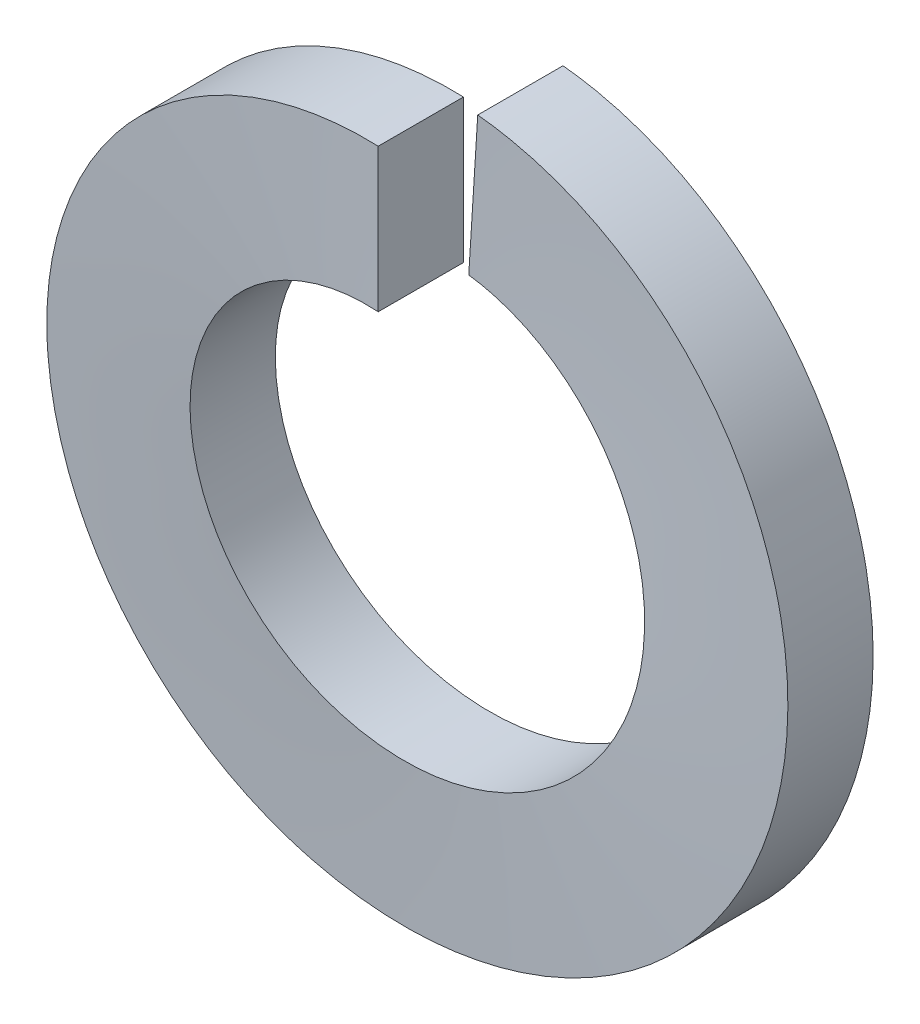
SolidWorks part; units mm, degrees
ref_plane "Front Plane" through (0, 0, 0) normal (0, 0, 1) x (1, 0, 0)
ref_plane "Top Plane" through (0, 0, 0) normal (0, 1, 0) x (1, 0, 0)
ref_plane "Right Plane" through (0, 0, 0) normal (1, 0, 0) x (0, 0, -1)
sketch "Sketch1" plane through (0, 0, 0) normal (0, 0, 1) x (1, 0, 0)
  line L0 (0, 9.05) -> (0, 5.35) construction
  line L2 (0, -2.1) -> (0, 2.1) construction
  circle A0 centre (0, 0) radius 9.05 construction
  circle A1 centre (0, 0) radius 5.35 construction
  point P6 (5.35, 0)
  point P7 (-9.05, 0)
  point P8 (-5.35, 0)
  point P9 (0, 0)
  point P10 (9.05, 0)
  point P14 (0, 0)
  point P15 (0, 2.1)
  point P16 (0, -2.1)
  dimension "Overall Height" = 4.2
  dimension "ID" = 10.7
  dimension "OD" = 18.1
sketch "Sketch2" plane through (0, 0, 0) normal (1, 0, 0) x (0, 0, -1)
  line L1 (0, 9.05) -> (-2.2, 9.05) construction
  line L2 (0, 9.05) -> (0, 5.35) construction
  line L3 (0, 5.35) -> (-2.2, 5.35) construction
  line L4 (-2.2, 9.05) -> (-2.2, 5.35) construction
  point P5 (-2.2, 9.05)
  point P8 (0, 9.05)
  point P9 (0, 5.35)
  point P10 (-2.2, 5.35)
  dimension "THK" = 2.2
sketch "Sketch3" plane through (0, 0, 0) normal (0, 0, 1) x (1, 0, 0)
  circle A0 centre (0, 0) radius 9.05 construction
  circle A1 centre (0, 0) radius 9.05
curve "Helix/Spiral1" pitch 2.0202 height 2 radius 9.05 left hand yes centre (0, 0, 0) axis (0, 0, -1) start towards (0, 1, 0) parameters "Height"=2
sketch "Sketch4" plane through (0, 0, 0) normal (1, 0, 0) x (0, 0, -1)
  line L0 (-2.2, 9.05) -> (-2.2, 5.35) construction
  line L1 (0, 9.05) -> (0, 5.35) construction
  line L2 (0, 5.35) -> (-2.2, 5.35) construction
  line L3 (0, 9.05) -> (-2.2, 9.05) construction
  line L4 (-2.2, 9.05) -> (-2.2, 5.35)
  line L5 (0, 9.05) -> (0, 5.35)
  line L6 (0, 5.35) -> (-2.2, 5.35)
  line L7 (0, 9.05) -> (-2.2, 9.05)
sweep "Sweep1" add profiles "Sketch4" path "Helix/Spiral1"
ref_axis "Center Axis 1" through (0, 0, -8.9167) along (0, 0, 1)
ref_plane "Contact Plane 1" through (0, 0, 2.2) normal (0, 0, 1) x (1, 0, 0)
ref_plane "Contact Plane 2" through (0, 0, -2) normal (0, 0, 1) x (1, 0, 0)
equation "\"Height@Helix/Spiral1\"=\"Overall Height@Sketch1\"-\"THK@Sketch2\""
